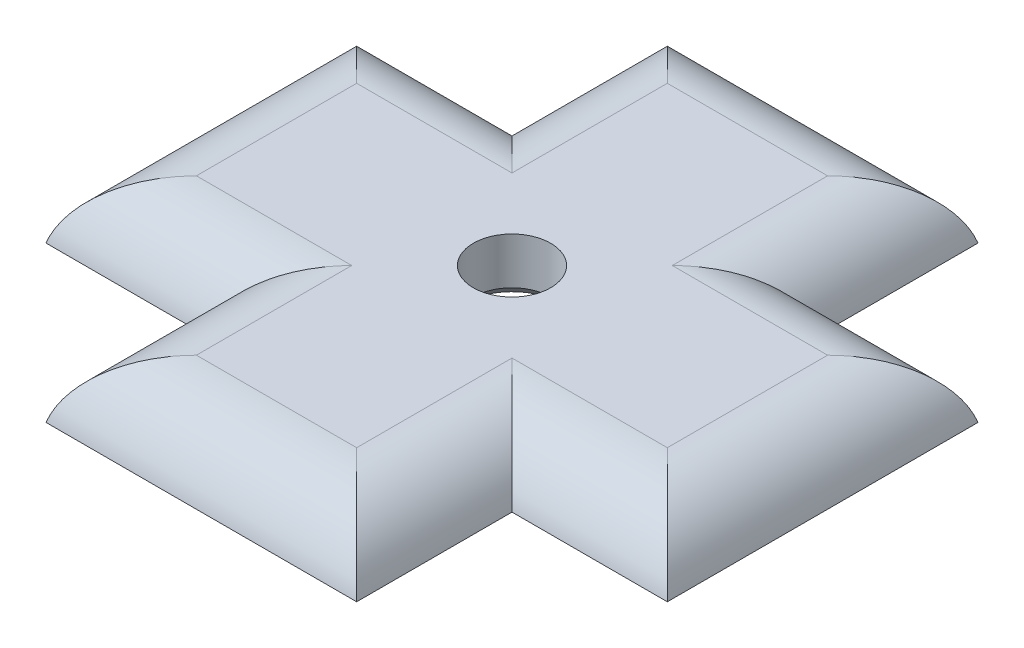
SolidWorks part; units mm, degrees
ref_plane "Front Plane" through (0, 0, 0) normal (0, 0, 1) x (1, 0, 0)
ref_plane "Top Plane" through (0, 0, 0) normal (0, 1, 0) x (1, 0, 0)
ref_plane "Right Plane" through (0, 0, 0) normal (1, 0, 0) x (0, 0, -1)
sketch "Sketch1" plane through (0, 0, 0) normal (0, 1, 0) x (1, 0, 0)
  line L1 (0, 0) -> (80, 0)
  line L2 (0, 0) -> (0, -80)
  line L3 (0, -80) -> (80, -80)
  line L4 (80, 0) -> (80, -80)
  line L5 (80, 0) -> (60, 0)
  line L6 (80, 0) -> (80, -20)
  line L7 (80, -20) -> (60, -20)
  line L8 (60, 0) -> (60, -20)
  line L9 (0, 0) -> (20, 0)
  line L10 (0, 0) -> (0, -20)
  line L11 (0, -20) -> (20, -20)
  line L12 (20, 0) -> (20, -20)
  line L13 (0, -80) -> (20, -80)
  line L14 (0, -80) -> (0, -60)
  line L15 (0, -60) -> (20, -60)
  line L16 (20, -80) -> (20, -60)
  line L21 (80, -80) -> (60, -80)
  line L22 (80, -80) -> (80, -60)
  line L23 (80, -60) -> (60, -60)
  line L24 (60, -80) -> (60, -60)
  dimension "D1" = 80
  dimension "D2" = 80
  dimension "D3" = 20
  dimension "D4" = 20
  dimension "D5" = 20
  dimension "D6" = 20
  dimension "D7" = 20
  dimension "D8" = 20
  dimension "D9" = 20
  dimension "D10" = 20
extrude "Boss-Extrude1" add sketch "Sketch1" along normal blind 7.5 contours L3 L24 L23 L4 L7 L8 L1 L12 L11 L2 L15 L16 region at (40, 0, 40)
fillet "Fillet1" radius 10 12 edges at (20, 7.5, 10) (40, 7.5, 0) (60, 7.5, 10) (70, 7.5, 20) (80, 7.5, 40) (70, 7.5, 60) (60, 7.5, 70) (40, 7.5, 80) (20, 7.5, 70) (10, 7.5, 60) (0, 7.5, 40) (10, 7.5, 20)
sketch "Sketch2" plane through (0, 0, 0) normal (0, 1, 0) x (1, 0, 0)
  line L0 (20, -80) -> (60, -80) construction
  line L1 (0, -20) -> (0, -60) construction
  circle A0 centre (40, -40) radius 4.975
  dimension "D1" = 9.95
  dimension "D2" = 40
  dimension "D3" = 40
extrude "Cut-Extrude1" cut sketch "Sketch2" along normal blind 7.5
chamfer "Chamfer1" distance 1.5 angle 45 1 edges at (40, 0, 44.975)
